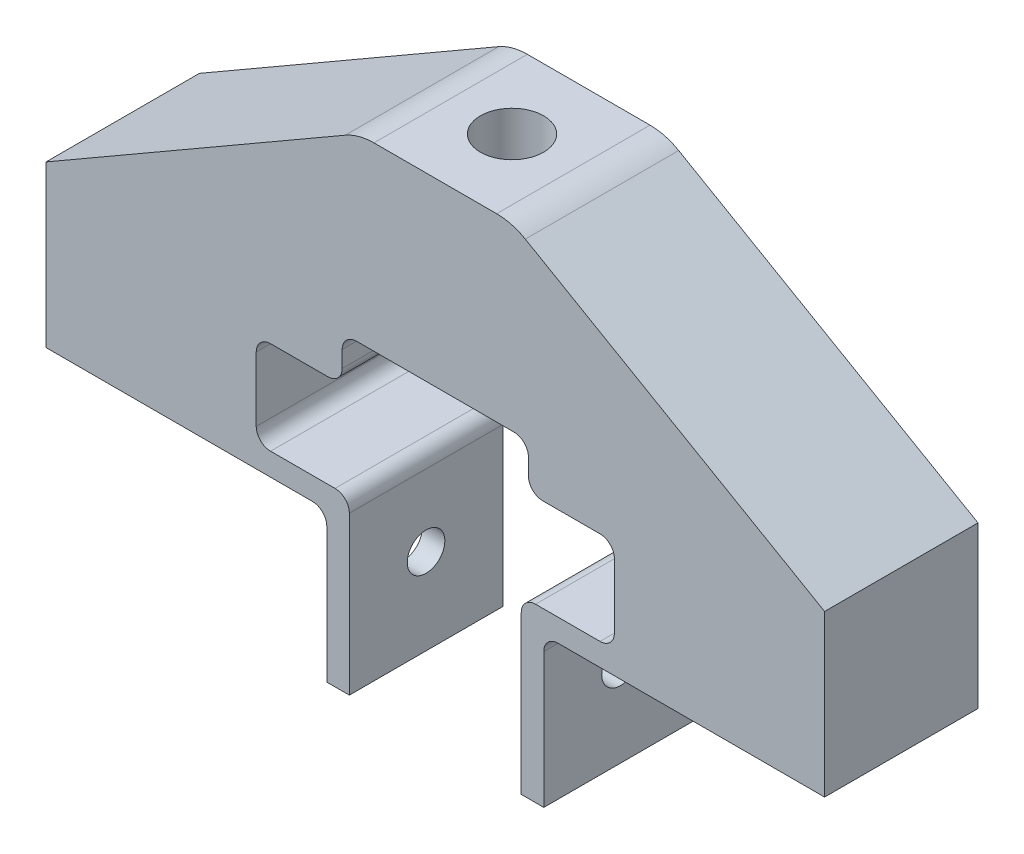
SolidWorks part; units mm, degrees
material "Polyester Resin"
ref_plane "Front Plane" through (0, 0, 0) normal (0, 0, 1) x (1, 0, 0)
ref_plane "Top Plane" through (0, 0, 0) normal (0, 1, 0) x (1, 0, 0)
ref_plane "Right Plane" through (0, 0, 0) normal (1, 0, 0) x (0, 0, -1)
sketch "Sketch1" plane through (0, 0, 0) normal (0, 0, 1) x (1, 0, 0)
  line L0 (-86.282, 0) -> (-24.05, 0)
  line L1 (-24.05, 0) -> (-24.05, -33.1)
  line L2 (-24.05, -33.1) -> (-19.05, -33.1)
  line L3 (-19.05, -33.1) -> (-19.05, 5)
  line L4 (-19.05, 5) -> (-39.6875, 5)
  line L5 (-39.6875, 5) -> (-39.6875, 25.6375)
  line L6 (-39.6875, 25.6375) -> (-20.6375, 25.6375)
  line L7 (39.6875, 25.6375) -> (39.6875, 5)
  line L8 (39.6875, 5) -> (19.05, 5)
  line L9 (19.05, 5) -> (19.05, -33.1)
  line L10 (19.05, -33.1) -> (24.05, -33.1)
  line L11 (24.05, -33.1) -> (24.05, 0)
  line L12 (24.05, 0) -> (86.282, 0)
  line L13 (86.282, 35.6375) -> (17, 75.6375)
  line L14 (17, 75.6375) -> (-17, 75.6375)
  line L15 (-17, 75.6375) -> (-86.282, 35.6375)
  line L16 (-20.6375, 25.6375) -> (-20.6375, 35.6375)
  line L17 (-20.6375, 35.6375) -> (20.6375, 35.6375)
  line L18 (20.6375, 35.6375) -> (20.6375, 25.6375)
  line L19 (20.6375, 25.6375) -> (39.6875, 25.6375)
  line L20 (86.282, 35.6375) -> (-86.282, 35.6375) construction
  line L21 (-86.282, 35.6375) -> (-86.282, 0)
  line L22 (86.282, 35.6375) -> (86.282, 0)
  point P18 (0, 75.6375)
  point P22 (0, 35.6375)
  dimension "D1" = 30
  dimension "D2" = 10
  dimension "D3" = 34
  dimension "D4" = 38.1
  dimension "D5" = 79.375
  dimension "D6" = 20.6375
  dimension "D7" = 5
  dimension "D8" = 5
  dimension "D9" = 38.1
  dimension "D10" = 41.275
  dimension "D11" = 40
extrude "Boss-Extrude1" add sketch "Sketch1" along normal blind 34
sketch "Sketch2" plane through (0, 75.6375, 0) normal (0, 1, 0) x (1, 0, 0)
  line L0 (-17, 0) -> (17, -34) construction
  line L1 (17, 0) -> (-17, -34) construction
  circle A0 centre (0, -17) radius 7
  dimension "D1" = 14
extrude "Cut-Extrude1" cut sketch "Sketch2" against normal blind 35
sketch "Sketch3" plane through (24.05, 0, 0) normal (1, 0, 0) x (0, 0, -1)
  line L0 (-17, -33.1) -> (-17, 0) construction
  line L1 (-34, -33.1) -> (0, -33.1) construction
  line L2 (-34, 0) -> (0, 0) construction
  circle A0 centre (-17, -14.05) radius 4.1656
  dimension "D1" = 8.3312
  dimension "D2" = 19.05
extrude "Cut-Extrude2" cut sketch "Sketch3" against normal through all
fillet "Fillet1" radius 3.175 12 edges at (-39.6875, 5, 17) (39.6875, 5, 17) (-20.6375, 35.6375, 17) (20.6375, 35.6375, 17) (39.6875, 25.6375, 17) (-39.6875, 25.6375, 17) (20.6375, 25.6375, 17) (-20.6375, 25.6375, 17) (24.05, 0, 17) (-24.05, 0, 17) (19.05, 5, 17) (-19.05, 5, 17)
fillet "Fillet2" radius 12.7 2 edges at (17, 75.6375, 17) (-17, 75.6375, 17)
